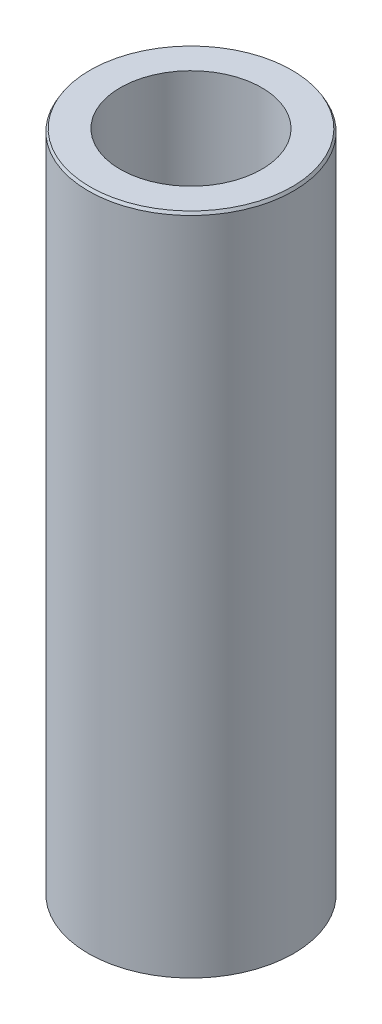
SolidWorks part; units mm, degrees
ref_plane "Front Plane" through (0, 0, 0) normal (0, 0, 1) x (1, 0, 0)
ref_plane "Top Plane" through (0, 0, 0) normal (0, 1, 0) x (1, 0, 0)
ref_plane "Right Plane" through (0, 0, 0) normal (1, 0, 0) x (0, 0, -1)
sketch "Sketch1" plane through (0, 0, 0) normal (0, 1, 0) x (1, 0, 0)
  circle A0 centre (0, 0) radius 40
  dimension "SHAFT_OD" = 80
extrude "Boss-Extrude1" add sketch "Sketch1" along normal blind 259.0756
sketch "Sketch2" plane through (0, 0, 0) normal (0, 1, 0) x (1, 0, 0)
  circle A0 centre (0, 0) radius 27.5809
  dimension "BORE_D" = 55.1618
extrude "Cut-Extrude1" cut sketch "Sketch2" along normal through all
chamfer "Chamfer1" distance 1.0915 angle 30 2 edges at (0, 259.0756, 40) (0, 0, 40) first distance on face at (0, 259.0756, 40) first distance on face at (0, 0, 27.5809)
